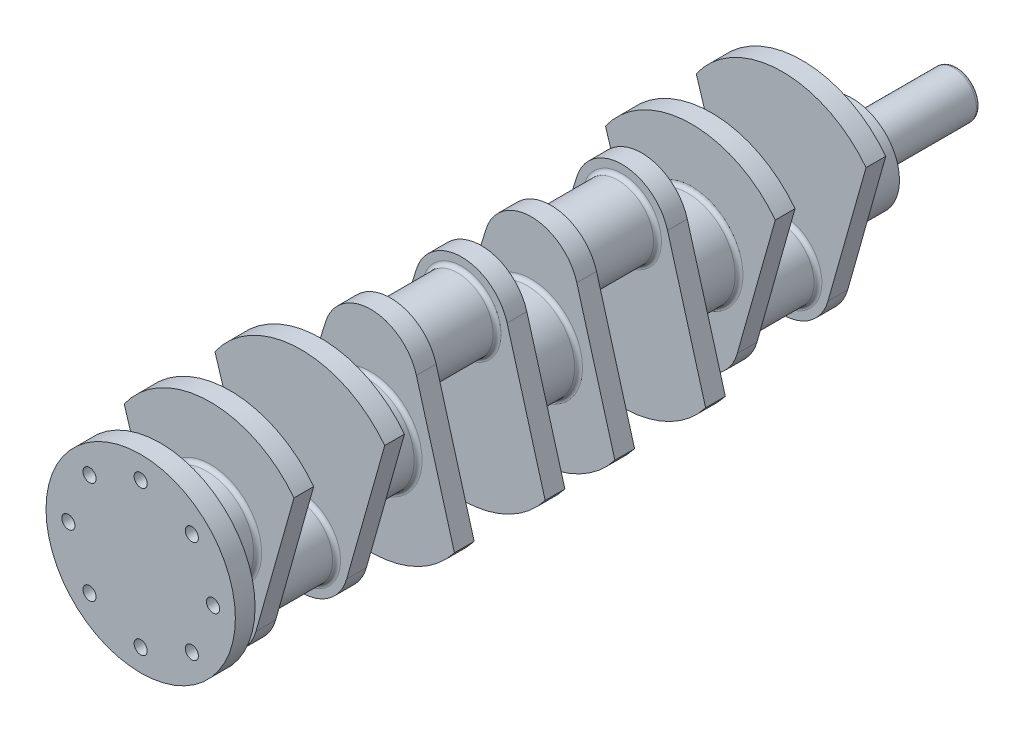
SolidWorks part; units mm, degrees
ref_plane "Ön Düzlem" through (0, 0, 0) normal (0, 0, 1) x (1, 0, 0)
ref_plane "Üst Düzlem" through (0, 0, 0) normal (0, 1, 0) x (1, 0, 0)
ref_plane "Sağ Düzlem" through (0, 0, 0) normal (1, 0, 0) x (0, 0, -1)
sketch "Çizim1" plane through (0, 0, 0) normal (0, 0, 1) x (1, 0, 0)
  line L0 (0, -44) -> (0, 80) construction
  line L1 (-65.4497, 0) -> (88.3471, 0) construction
  line L2 (-34.3865, -54.6569) -> (-65.542, 45.872)
  line L3 (34.6431, -53.7906) -> (63.5706, 48.5672)
  arc A0 (-34.3865, -54.6569) -> (34.6431, -53.7906) centre (0, -44) ccw
  arc A1 (-65.542, 45.872) -> (63.5706, 48.5672) centre (0, 0) cw
  dimension "D2" = 72
  dimension "D4" = 80
  dimension "D1" = 44
  dimension "D3" = 33
extrude "Yükseklik-Ekstrüzyon1" add sketch "Çizim1" along normal blind 15
sketch "Çizim2" plane through (0, 0, 0) normal (0, 0, -1) x (-1, 0, 0)
  circle A0 centre (0, -44) radius 27
  dimension "D1" = 54
extrude "Yükseklik-Ekstrüzyon2" add sketch "Çizim2" along normal blind 54
sketch "Çizim3" plane through (0, 0, 15) normal (0, 0, 1) x (1, 0, 0)
  circle A0 centre (0, 0) radius 36
  dimension "D1" = 72
extrude "Yükseklik-Ekstrüzyon3" add sketch "Çizim3" along normal blind 38
ref_plane "Düzlem1" through (0, 0, -27) normal (0, 0, -1) x (-1, 0, 0)
mirror "Aynalama1" about plane through (0, 0, -27) normal (0, 0, -1) of "Yükseklik-Ekstrüzyon3", "Yükseklik-Ekstrüzyon1"
ref_plane "Düzlem2" through (0, 0, 34) normal (0, 0, 1) x (1, 0, 0)
mirror "Aynalama4" about plane through (0, 0, 34) normal (0, 0, 1) of bodies 105
move or copy body "Gövde-Taşı/Kopyala1" bodies to move or copy 110 copy no rotation origin (0, 0, 95) rotation axis (1, 0, 0) rotation angle 180
ref_plane "Düzlem3" through (0, 0, 156) normal (0, 0, 1) x (1, 0, 0)
mirror "Aynalama5" about plane through (0, 0, 156) normal (0, 0, 1) of bodies 105 111
sketch "Çizim4" plane through (0, 0, -107) normal (0, 0, -1) x (-1, 0, 0)
  circle A0 centre (0, 0) radius 17.5
  dimension "D1" = 35
extrude "Yükseklik-Ekstrüzyon4" add sketch "Çizim4" along normal blind 80
sketch "Çizim5" plane through (0, 0, 419) normal (0, 0, 1) x (1, 0, 0)
  circle A0 centre (0, 0) radius 72
  circle A1 centre (0, 0) radius 55 construction
  circle A2 centre (0, 55) radius 5
  circle A3 centre (38.8909, 38.8909) radius 5
  circle A4 centre (55, 0) radius 5
  circle A5 centre (38.8909, -38.8909) radius 5
  circle A6 centre (0, -55) radius 5
  circle A7 centre (-38.8909, -38.8909) radius 5
  circle A8 centre (-55, 0) radius 5
  circle A9 centre (-38.8909, 38.8909) radius 5
  circle A10 centre (0, 0) radius 36 construction
  point P23 (0, 0)
  dimension "D1" = 144
  dimension "D2" = 110
  dimension "D3" = 10
  dimension "D4" = 8
extrude "Yükseklik-Ekstrüzyon5" add sketch "Çizim5" along normal blind 15
combine bodies "Birleştir1" operation type add bodies to combine 114 111 113 115
fillet "Radyus1" radius 3 19 edges at (36, 0, 381) (36, 0, 419) (-27, -44, 366) (27, -44, 312) (36, 0, 297) (36, 0, 259) (-27, 44, 244) (27, 44, 190) (36, 0, 175) (-27, 44, 68) (27, 44, 122) (36, 0, 137) (36, 0, -69) (36, 0, 53) (-27, -44, -54) (27, -44, 0) (36, 0, 15) (-17.5, 0, -107) (-17.5, 0, -187)
